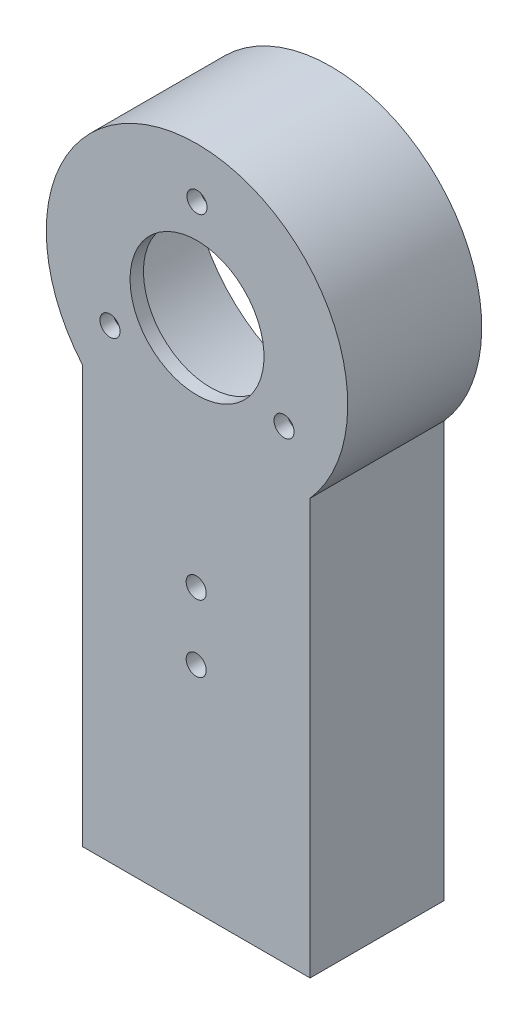
SolidWorks part; units mm, degrees
ref_plane "Front Plane" through (0, 0, 0) normal (0, 0, 1) x (1, 0, 0)
ref_plane "Top Plane" through (0, 0, 0) normal (0, 1, 0) x (1, 0, 0)
ref_plane "Right Plane" through (0, 0, 0) normal (1, 0, 0) x (0, 0, -1)
sketch "Sketch1" plane through (0, 0, 0) normal (0, 0, 1) x (1, 0, 0)
  line L1 (-17.1236, -14.5956) -> (-17.1236, -76.9)
  line L2 (16.8764, -14.8808) -> (16.8764, -76.9)
  line L3 (-17.1236, -76.9) -> (16.8764, -76.9)
  circle A0 centre (0, 0) radius 22.5
  arc A1 (-17.1236, -14.5956) -> (16.8764, -14.8808) centre (0, 0) ccw
  circle A2 centre (-0.1236, -44.9) radius 1.5
  circle A3 centre (-0.1236, -34.9) radius 1.5
  dimension "D1" = 45
  dimension "D4" = 3
  dimension "D5" = 3
  dimension "D6" = 32
  dimension "D7" = 42
  dimension "D2" = 76.9
  dimension "D3" = 34
extrude "Boss-Extrude1" add sketch "Sketch1" along normal blind 20 contours A0 L1 L3 L2 | A0 L1 region at (-0.1354, -48.5303, 0) region at (0, 0, 0)
sketch "Sketch2" plane through (0, 0, 0) normal (0, 0, -1) x (-1, 0, 0)
  circle A0 centre (0, 0) radius 10
  dimension "D1" = 20
extrude "Cut-Extrude1" cut sketch "Sketch2" against normal blind 20
sketch "Sketch3" plane through (0, 0, 0) normal (0, 0, -1) x (-1, 0, 0)
  circle A0 centre (0, 15) radius 1.5
  circle A1 centre (12.9904, -7.5) radius 1.5
  circle A2 centre (-12.9904, -7.5) radius 1.5
  point P10 (0, 0)
  dimension "D1" = 3
  dimension "D2" = 15
  dimension "D3" = 3
extrude "Cut-Extrude2" cut sketch "Sketch3" against normal blind 20
sketch "Sketch4" plane through (0, 0, 0) normal (0, 0, -1) x (-1, 0, 0)
  circle A0 centre (0, 0) radius 21
  dimension "D1" = 42
extrude "Cut-Extrude3" cut sketch "Sketch4" against normal blind 18
sketch "Sketch5" plane through (0, -76.9, 0) normal (0, -1, 0) x (1, 0, 0)
  line L0 (-17.1236, 20) -> (-17.1236, 0) construction
  line L1 (16.8764, 20) -> (16.8764, 0) construction
  line L2 (-0.1236, 20) -> (-0.1236, 0) construction
  line L3 (-17.1236, 20) -> (16.8764, 20) construction
  line L4 (-17.1236, 0) -> (16.8764, 0) construction
  circle A0 centre (-7.1236, 10) radius 1.5
  circle A1 centre (6.8764, 10) radius 1.5
  dimension "D1" = 3
  dimension "D2" = 3
  dimension "D5" = 7
  dimension "D6" = 10
  dimension "D3" = 10
  dimension "D4" = 10
extrude "Cut-Extrude4" cut sketch "Sketch5" against normal blind 15
